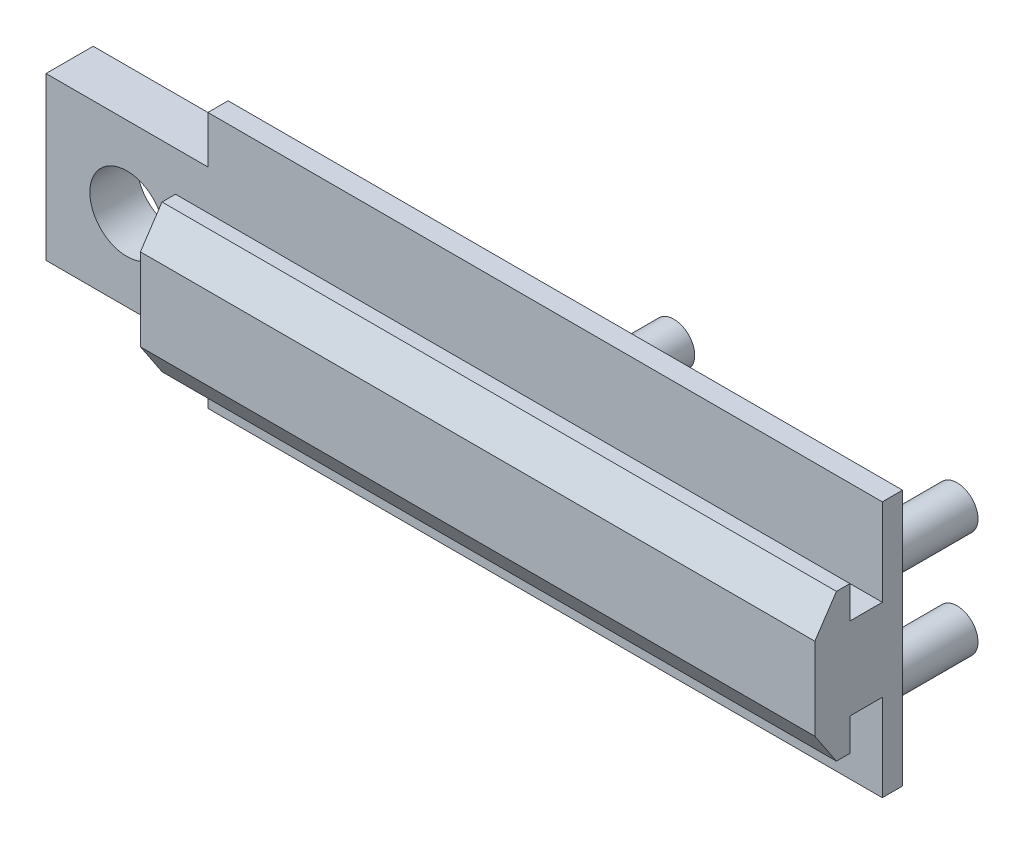
SolidWorks part; units mm, degrees
ref_plane "Front Plane" through (0, 0, 0) normal (0, 0, 1) x (1, 0, 0)
ref_plane "Top Plane" through (0, 0, 0) normal (0, 1, 0) x (1, 0, 0)
ref_plane "Right Plane" through (0, 0, 0) normal (1, 0, 0) x (0, 0, -1)
sketch "Sketch1" plane through (0, 0, 0) normal (0, 1, 0) x (1, 0, 0)
  line L1 (-25, 3.25) -> (25, 3.25)
  line L2 (-25, 3.25) -> (-25, -3.25)
  line L3 (-25, -3.25) -> (25, -3.25)
  line L4 (25, 3.25) -> (25, -3.25)
  line L5 (-25, 3.25) -> (25, -3.25) construction
  line L6 (-25, -3.25) -> (25, 3.25) construction
  point P0 (0, 0)
  dimension "D1" = 50
  dimension "D2" = 6.5
extrude "Boss-Extrude1" add sketch "Sketch1" along normal blind 19
sketch "Sketch2" plane through (25, 0, 0) normal (1, 0, 0) x (0, 0, -1)
  line L0 (-3.25, 9.5) -> (1.75, 9.5) construction
  line L1 (-3.25, 19) -> (-3.25, 0) construction
  line L2 (1.75, 12.55) -> (1.75, 6.45) construction
  line L3 (1.75, 12.55) -> (-0.65, 12.55)
  line L4 (1.75, 6.45) -> (-0.65, 6.45)
  line L5 (-0.65, 12.55) -> (-0.65, 14.95)
  line L6 (-0.65, 14.95) -> (-1.65, 14.95)
  line L7 (-0.65, 6.45) -> (-0.65, 4.05)
  line L8 (-0.65, 4.05) -> (-1.65, 4.05)
  line L9 (1.75, 12.55) -> (1.75, 19)
  line L10 (-3.25, 19) -> (3.25, 19) construction
  line L11 (1.75, 6.45) -> (1.75, 0)
  line L12 (-3.25, 0) -> (3.25, 0) construction
  line L13 (-0.65, 12.55) -> (-3.25, 12.55) construction
  line L14 (-1.65, 14.95) -> (-3.25, 12.55)
  line L15 (-0.65, 6.45) -> (-3.25, 6.45) construction
  line L16 (-1.65, 4.05) -> (-3.25, 6.45)
  line L17 (-3.25, 6.45) -> (-3.25, 12.55)
  point P7 (1.75, 9.5)
  point P8 (-3.25, 9.5)
  dimension "D1" = 5
  dimension "D2" = 6.1
  dimension "D3" = 2.4
  dimension "D4" = 2.4
  dimension "D5" = 1
extrude "Cut-Extrude1" cut sketch "Sketch2" along direction (-1, 0, 0) on the side against the normal through all and the other way through all
sketch "Sketch3" plane through (-25, 0, 0) normal (-1, 0, 0) x (0, 0, 1)
  line L6 (-1.75, 12.55) -> (-1.75, 6.45) construction
  line L7 (-1.75, 9.5) -> (-3.5, 9.5) construction
  line L8 (-1.75, 6.45) -> (-1.75, 0) construction
  line L9 (-5.25, 15.5) -> (-1.75, 15.5)
  line L10 (-5.25, 15.5) -> (-5.25, 3.5)
  line L11 (-5.25, 3.5) -> (-1.75, 3.5)
  line L12 (-1.75, 15.5) -> (-1.75, 3.5)
  line L13 (-5.25, 15.5) -> (-1.75, 3.5) construction
  line L14 (-5.25, 3.5) -> (-1.75, 15.5) construction
  dimension "D1" = 12
  dimension "D2" = 3.5
extrude "Boss-Extrude2" add sketch "Sketch3" along normal blind 12
sketch "Sketch4" plane through (0, 0, -5.25) normal (0, 0, -1) x (-1, 0, 0)
  line L0 (31, 9.5) -> (37, 9.5) construction
  line L1 (37, 15.5) -> (37, 3.5) construction
  line L2 (31, 9.5) -> (31, 3.5) construction
  line L3 (37, 3.5) -> (25, 3.5) construction
  circle A0 centre (31, 9.5) radius 2.75
  dimension "D1" = 5.5
extrude "Cut-Extrude2" cut sketch "Sketch4" against normal up to next contours A0
sketch "Sketch6" plane through (0, 0, -3.25) normal (0, 0, -1) x (-1, 0, 0)
  line L0 (-25, 0) -> (-25, 11) construction
  line L1 (-25, 0) -> (25, 0) construction
  line L2 (-25, 19) -> (-25, 0) construction
  line L3 (-25.5445, 5.55) -> (-22.5445, 5.55) construction
  line L4 (-25, 11) -> (25, 11)
  line L5 (-25, 11) -> (-25, 0)
  line L6 (-25, 0) -> (25, 0)
  line L7 (25, 11) -> (25, 0)
  line L8 (-22.5445, 4) -> (-22.5445, 0) construction
  line L10 (-22.5445, 5.55) -> (-1.5445, 5.55) construction
  circle A0 centre (-22.5445, 5.55) radius 1.55
  circle A1 centre (-1.5445, 5.55) radius 1.55
  dimension "D5" = 3.1
  dimension "D1" = 11
  dimension "D2" = 4
  dimension "D3" = 21
  dimension "D4" = 3
extrude "Boss-Extrude3" add sketch "Sketch6" along normal blind 6.5 contours A0 | A1 region at (22.5445, 5.55, -3.25) region at (1.5445, 5.55, -3.25)
fillet "Fillet2" radius 10 1 edges at (-25, 9.5, -3.25)
ref_plane "Plane1" through (0, 9.5, 0) normal (0, 1, 0) x (1, 0, 0)
mirror "Mirror1" about plane through (0, 9.5, 0) normal (0, 1, 0) of "Boss-Extrude3"
